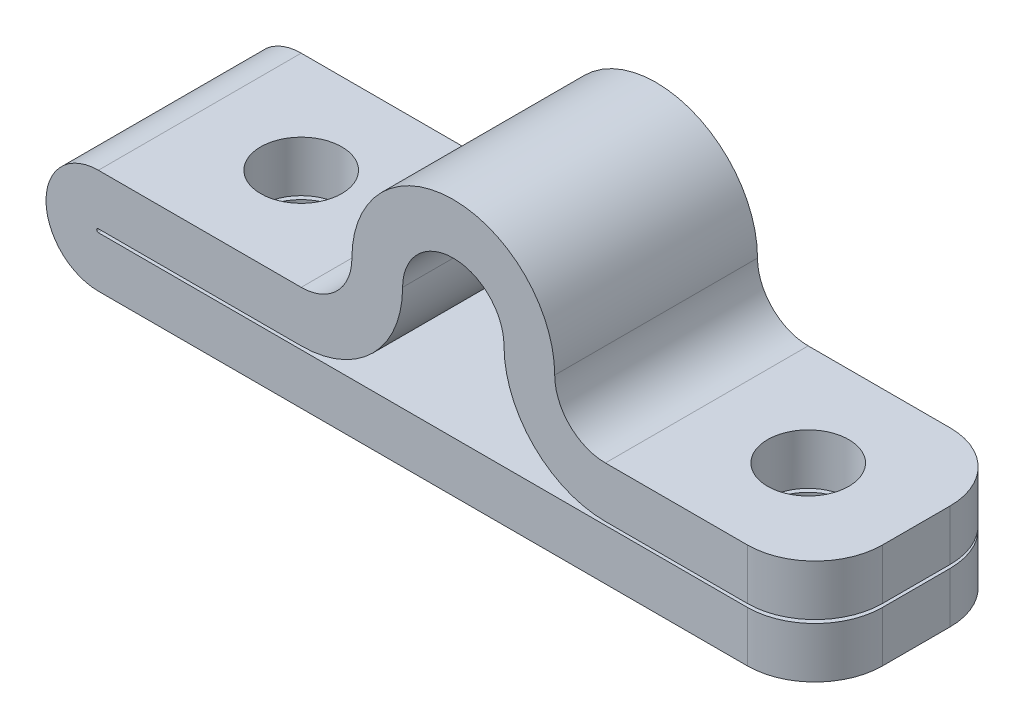
SolidWorks part; units mm, degrees
material "PLA"
ref_plane "Plan de face" through (0, 0, 0) normal (0, 0, 1) x (1, 0, 0)
ref_plane "Plan de dessus" through (0, 0, 0) normal (0, 1, 0) x (1, 0, 0)
ref_plane "Plan de droite" through (0, 0, 0) normal (1, 0, 0) x (0, 0, -1)
sketch "Sketch1" plane through (0, 0, 0) normal (0, 0, 1) x (1, 0, 0)
  line L0 (-10.5, 0) -> (10.7, 0)
  line L1 (10.7, 0) -> (10.7, 1.5)
  line L2 (10.7, 1.5) -> (-10.5, 1.5)
  line L3 (-10.5, 1.6) -> (-4.5, 1.6)
  line L4 (4.5, 1.6) -> (10.7, 1.6)
  line L5 (-7.5, 8.5621) -> (-7.5, -5.9396) construction
  line L6 (7.5, -6.0625) -> (7.5, 8.685) construction
  line L7 (6.3, 3.1) -> (6.3, 0) construction
  line L8 (8.7, 3.1) -> (8.7, 0) construction
  line L9 (-6.3, 3.1) -> (-6.3, 0) construction
  line L10 (-8.7, 3.1) -> (-8.7, 0) construction
  line L11 (10.7, 1.6) -> (10.7, 3.1)
  line L12 (10.7, 3.1) -> (4.5, 3.1)
  line L14 (-10.5, 3.1) -> (-4.5, 3.1)
  arc A0 (-10.5, 0) -> (-10.5, 3.1) centre (-10.5, 1.55) cw
  arc A1 (-10.5, 1.5) -> (-10.5, 1.6) centre (-10.5, 1.55) cw
  arc A2 (4.5, 1.6) -> (1.5, 4.6) centre (4.5, 4.6) cw
  arc A3 (1.5, 4.6) -> (0, 6.1) centre (0, 4.6) ccw
  arc A4 (0, 6.1) -> (-1.5, 4.6) centre (0, 4.6) ccw
  arc A5 (-1.5, 4.6) -> (-4.5, 1.6) centre (-4.5, 4.6) cw
  arc A6 (-4.5, 3.1) -> (-3, 4.6) centre (-4.5, 4.6) ccw
  arc A7 (-3, 4.6) -> (0, 7.6) centre (0, 4.6) cw
  arc A8 (4.5, 3.1) -> (3, 4.6) centre (4.5, 4.6) cw
  arc A9 (3, 4.6) -> (0, 7.6) centre (0, 4.6) ccw
  point P29 (7.5, 3.1)
  point P56 (-7.5, 3.1)
  dimension "D12" = 3
  dimension "D13" = 3
  dimension "D1" = 1.5
  dimension "D2" = 15
  dimension "D3" = 7.5
  dimension "D4" = 2.4
  dimension "D5" = 1.2
  dimension "D6" = 2.4
  dimension "D7" = 1.2
  dimension "D8" = 2
  dimension "D9" = 0.1
  dimension "D10" = 3
  dimension "D11" = 3
extrude "Boss-Extrude1" add sketch "Sketch1" along normal mid plane 6 contours A8 A9 A7 A6 L14 A0 L0 L1 L2 A1 L3 A5 A4 A3 A2 L4 L11 L12 region at (-11.8101, 1.55, 0)
sketch "Sketch4" plane through (0, 3.1, 0) normal (0, 1, 0) x (1, 0, 0)
  line L0 (-10.5, 0) -> (10.7, 0) construction
  line L1 (10.7, 0) -> (4.5, 0) construction
  point P0 (-7.5, 0)
  point P4 (7.5, 0)
hole_wizard "M2 Clearance Hole1" positions "Sketch4" profile "Sketch5" hole size "M2" standard "ANSI Metric" end condition through all
sketch "Sketch5" plane through (-7.5, 3.1, 0) normal (1, 0, 0) x (0, 0, 1)
  line L0 (0, 0) -> (0, 3.1)
  line L1 (0, 3.1) -> (1.2, 3.1)
  line L2 (1.2, 3.1) -> (1.2, 0)
  line L5 (1.2, 0) -> (0, 0)
  line L11 (0, -6.35) -> (0, 107.95) construction
  dimension "Thru Hole Dia." = 2.4
  dimension "Thru Hole Depth" = 3.1
fillet "Fillet1" radius 2 4 edges at (10.7, 0.75, -3) (10.7, 2.35, -3) (10.7, 2.35, 3) (10.7, 0.75, 3)
